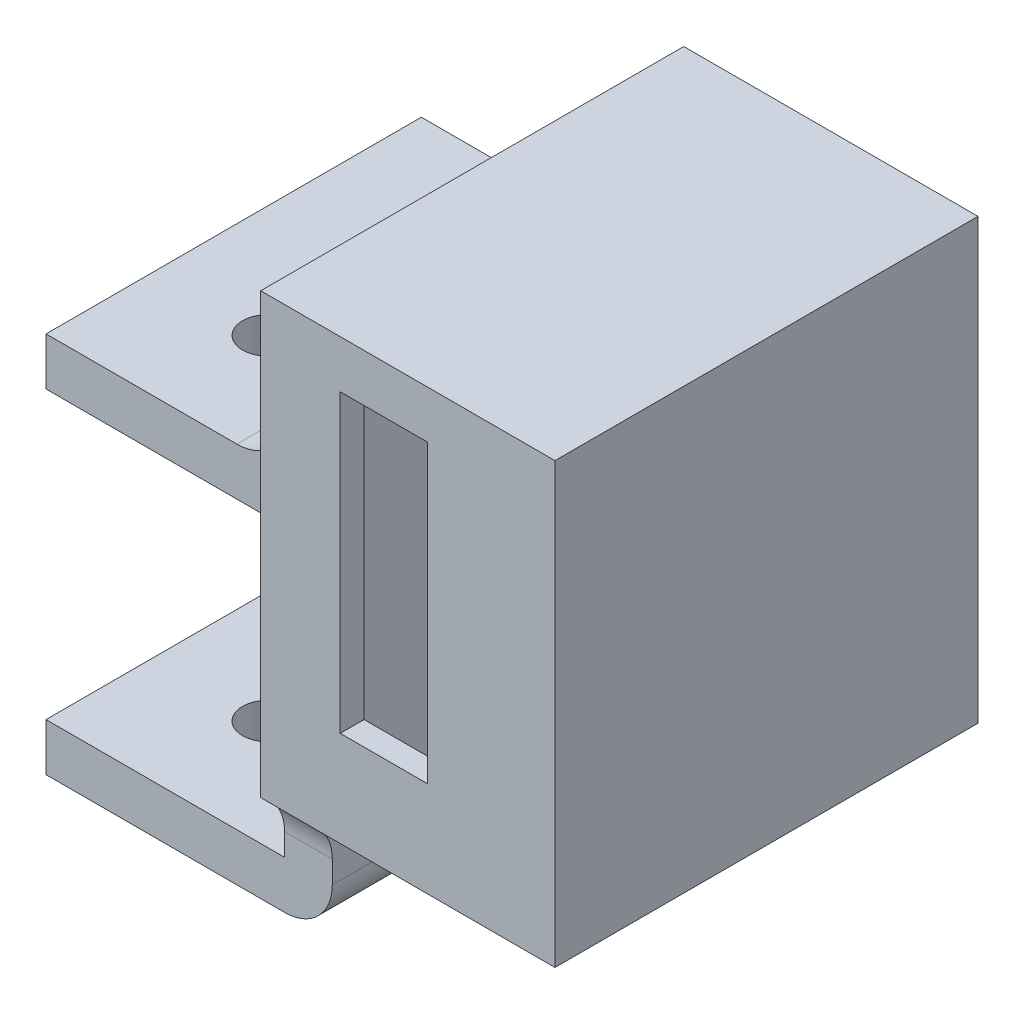
SolidWorks part; units mm, degrees
material "Custom Plastic"
ref_plane "Front Plane" through (0, 0, 0) normal (0, 0, 1) x (1, 0, 0)
ref_plane "Top Plane" through (0, 0, 0) normal (0, 1, 0) x (1, 0, 0)
ref_plane "Right Plane" through (0, 0, 0) normal (1, 0, 0) x (0, 0, -1)
sketch "Sketch1" plane through (0, 0, 0) normal (1, 0, 0) x (0, 0, -1)
  line L1 (-11.8, -12.3) -> (11.8, -12.3)
  line L2 (-11.8, -12.3) -> (-11.8, 12.3)
  line L3 (-11.8, 12.3) -> (11.8, 12.3)
  line L4 (11.8, -12.3) -> (11.8, 12.3)
  line L5 (-11.8, -12.3) -> (11.8, 12.3) construction
  line L6 (-11.8, 12.3) -> (11.8, -12.3) construction
  line L7 (-13.3, -13.8) -> (13.3, -13.8)
  line L8 (-13.3, -13.8) -> (-13.3, 13.8)
  line L9 (-13.3, 13.8) -> (13.3, 13.8)
  line L10 (13.3, -13.8) -> (13.3, 13.8)
  line L11 (-13.3, -13.8) -> (13.3, 13.8) construction
  line L12 (-13.3, 13.8) -> (13.3, -13.8) construction
  point P0 (0, 0)
  point P6 (0, 0)
  dimension "D1" = 24.6
  dimension "D2" = 23.6
  dimension "D3" = 26.6
  dimension "D4" = 24.6
  dimension "D5" = 27.6
extrude "Boss-Extrude1" add sketch "Sketch1" along normal blind 12.5
sketch "Sketch2" plane through (0, 0, 0) normal (-1, 0, 0) x (0, 0, 1)
  line L1 (-13.3, 13.8) -> (13.3, 13.8)
  line L2 (-13.3, 13.8) -> (-13.3, -13.8)
  line L3 (-13.3, -13.8) -> (13.3, -13.8)
  line L4 (13.3, 13.8) -> (13.3, -13.8)
extrude "Boss-Extrude2" add sketch "Sketch2" along normal blind 3
sketch "Sketch3" plane through (0, 0, -13.3) normal (0, 0, -1) x (-1, 0, 0)
sketch "Sketch4" plane through (12.5, 0, 0) normal (1, 0, 0) x (0, 0, -1)
  line L1 (-13.3, 13.8) -> (13.3, 13.8)
  line L2 (-13.3, 13.8) -> (-13.3, -13.8)
  line L3 (-13.3, -13.8) -> (13.3, -13.8)
  line L4 (13.3, 13.8) -> (13.3, -13.8)
extrude "Boss-Extrude3" add sketch "Sketch4" along normal blind 3
sketch "Sketch6" plane through (0, -13.8, 0) normal (0, -1, 0) x (-1, 0, 0)
  line L0 (0, 14.63) -> (0, -14.63) construction
  line L1 (0, -10.3) -> (-12.5, -10.3)
  line L2 (0, -10.3) -> (0, 10.3)
  line L3 (0, 10.3) -> (-12.5, 10.3)
  line L4 (-12.5, -10.3) -> (-12.5, 10.3)
  line L5 (-15.5, -13.3) -> (3, -13.3) construction
  line L6 (3, 13.3) -> (3, -13.3) construction
  line L7 (-15.5, -13.3) -> (-15.5, 13.3) construction
  line L8 (-15.5, 13.3) -> (3, 13.3) construction
  dimension "D1" = 3
  dimension "D2" = 3
  dimension "D3" = 3
  dimension "D4" = 3
extrude "Cut-Extrude1" cut sketch "Sketch6" against normal blind 3
sketch "Sketch7" plane through (0, -13.8, 0) normal (0, -1, 0) x (-1, 0, 0)
  line L0 (1.2891, -13.3) -> (1.2891, -4.9) construction
  line L1 (-15.5, -13.3) -> (3, -13.3) construction
  line L2 (1.2891, -4.9) -> (1.2891, 4.9) construction
  line L3 (1.2891, 4.9) -> (1.2891, 13.3) construction
  line L4 (-15.5, 13.3) -> (3, 13.3) construction
  line L5 (0, 14.63) -> (0, -14.63) construction
  line L6 (0, -7.4191) -> (12.54, -7.4191)
  line L7 (0, -7.4191) -> (0, 6.9729)
  line L8 (0, 6.9729) -> (12.54, 6.9729)
  line L9 (12.54, -7.4191) -> (12.54, 6.9729)
  dimension "D1" = 8.4
  dimension "D2" = 9.8
  dimension "D3" = 8.4
  dimension "D4" = 12.54
extrude "Boss-Extrude4" add sketch "Sketch7" along normal blind 7 and the other way blind 17
sketch "Sketch8" plane through (0, -20.8, 0) normal (0, -1, 0) x (-1, 0, 0)
  line L0 (12.54, 4.9005) -> (12.54, -4.9633)
  circle A0 centre (9.94, -4.9005) radius 1.6
  circle A1 centre (9.94, 4.8367) radius 1.6
  point P3 (12.54, -0.0633)
  point P8 (12.54, 0)
  dimension "D3" = 3.2
  dimension "D4" = 3.2
extrude "Cut-Extrude2" cut sketch "Sketch8" against normal through all contours A0 | A1 region at (-9.94, -20.8, 4.9005) region at (-9.94, -20.8, -4.8367)
sketch "Sketch10" plane through (0, 0, 7.4191) normal (0, 0, 1) x (1, 0, 0)
  line L0 (-12.54, 3.2) -> (-12.54, -20.8) construction
  line L1 (-12.54, 0.2) -> (-3, 0.2)
  line L2 (-12.54, 0.2) -> (-12.54, -17.8)
  line L3 (-12.54, -17.8) -> (-3, -17.8)
  line L4 (-3, 0.2) -> (-3, -17.8)
  line L5 (0, -20.8) -> (-12.54, -20.8) construction
  dimension "D1" = 3
  dimension "D2" = 3
  dimension "D3" = 18
extrude "Cut-Extrude3" cut sketch "Sketch10" against normal through all
sketch "Sketch11" plane through (0, 0, 13.3) normal (0, 0, 1) x (1, 0, 0)
  line L0 (-3, -13.8) -> (-3, 13.8) construction
  line L1 (2, 10.8) -> (7.5, 10.8)
  line L2 (2, 10.8) -> (2, -7.8)
  line L3 (2, -7.8) -> (7.5, -7.8)
  line L4 (7.5, 10.8) -> (7.5, -7.8)
  line L5 (15.5, 13.8) -> (15.5, -13.8) construction
  line L6 (15.5, 13.8) -> (-3, 13.8) construction
  line L7 (15.5, -13.8) -> (-3, -13.8) construction
  dimension "D1" = 5
  dimension "D2" = 8
  dimension "D3" = 3
  dimension "D4" = 6
sketch "Sketch14" plane through (0, -13.8, 0) normal (0, -1, 0) x (-1, 0, 0)
  line L0 (0, 14.63) -> (0, -14.63) construction
  line L1 (-12.5, -11.8) -> (0, -11.8)
  line L2 (-12.5, -11.8) -> (-12.5, 11.8)
  line L3 (-12.5, 11.8) -> (0, 11.8)
  line L4 (0, -11.8) -> (0, 11.8)
  line L5 (-15.5, -13.3) -> (3, -13.3) construction
  line L6 (-15.5, 13.3) -> (3, 13.3) construction
  dimension "D1" = 1.5
  dimension "D2" = 1.5
extrude "Cut-Extrude5" cut sketch "Sketch14" against normal blind 3
sketch "Sketch16" plane through (0, 0, 13.3) normal (0, 0, 1) x (1, 0, 0)
  line L1 (2, 10.8) -> (7.5, 10.8)
  line L2 (2, 10.8) -> (2, -7.8)
  line L3 (2, -7.8) -> (7.5, -7.8)
  line L4 (7.5, 10.8) -> (7.5, -7.8)
extrude "Cut-Extrude6" cut sketch "Sketch16" against normal blind 3
sketch "Sketch17" plane through (0, -13.8, 0) normal (0, -1, 0) x (-1, 0, 0)
  line L0 (0, 14.63) -> (0, -14.63) construction
  line L1 (-15.5, -13.3) -> (0, -13.3)
  line L2 (-15.5, -13.3) -> (-15.5, 13.3)
  line L3 (-15.5, 13.3) -> (0, 13.3)
  line L4 (0, -13.3) -> (0, 13.3)
  line L5 (-15.5, 13.3) -> (3, 13.3) construction
sketch "Sketch24" plane through (0, -13.8, 0) normal (0, -1, 0) x (-1, 0, 0)
  line L0 (0, -13.3) -> (0, 13.3) construction
  line L1 (3, -13.3) -> (0, -13.3)
  line L2 (3, -13.3) -> (3, -7.4191)
  line L3 (3, -7.4191) -> (0, -7.4191)
  line L4 (0, -13.3) -> (0, -7.4191)
  line L5 (0, -7.4191) -> (12.54, -7.4191) construction
extrude "Boss-Extrude7" add sketch "Sketch24" along normal blind 7
sketch "Sketch25" plane through (0, -13.8, 0) normal (0, -1, 0) x (-1, 0, 0)
  line L1 (0, 13.3) -> (3, 13.3)
  line L2 (0, 13.3) -> (0, 6.9729)
  line L3 (0, 6.9729) -> (3, 6.9729)
  line L4 (3, 13.3) -> (3, 6.9729)
extrude "Boss-Extrude8" add sketch "Sketch25" along normal blind 7
sketch "Sketch27" plane through (-3, 0, 0) normal (-1, 0, 0) x (0, 0, 1)
  line L0 (-13.3, 13.8) -> (-13.3, -20.8) construction
  line L1 (-13.3, -17.8) -> (13.3, -17.8)
  line L2 (-13.3, -17.8) -> (-13.3, -20.8)
  line L3 (-13.3, -20.8) -> (13.3, -20.8)
  line L4 (13.3, -17.8) -> (13.3, -20.8)
extrude "Boss-Extrude9" add sketch "Sketch27" along normal blind 20
sketch "Sketch29" plane through (0, -17.8, 0) normal (0, 1, 0) x (1, 0, 0)
  line L0 (-9.94, 4.8367) -> (-9.94, -4.9005)
  line L1 (-9.94, 4.8367) -> (-10.64, 4.8367) construction
  dimension "D1" = 0.7
sketch "Sketch30" plane through (0, -17.8, 0) normal (0, 1, 0) x (1, 0, 0)
  line L0 (-10.64, 4.8367) -> (-10.64, -4.9005)
sketch "Sketch32" plane through (-3, 0, 0) normal (-1, 0, 0) x (0, 0, 1)
  line L0 (-13.3, 13.8) -> (-13.3, -17.8) construction
  line L1 (-13.3, 3.2) -> (13.3, 3.2)
  line L2 (-13.3, 3.2) -> (-13.3, 0.2)
  line L3 (-13.3, 0.2) -> (13.3, 0.2)
  line L4 (13.3, 3.2) -> (13.3, 0.2)
  line L5 (13.3, 10.8) -> (13.3, -7.8) construction
extrude "Boss-Extrude10" add sketch "Sketch32" along normal blind 20
fillet "Fillet1" radius 3 1 edges at (0, -20.8, 0)
sketch "Sketch35" plane through (0, 0, 13.3) normal (0, 0, 1) x (1, 0, 0)
  line L1 (-3, 3.2) -> (-23, 3.2)
  line L2 (-3, 3.2) -> (-3, -20.8)
  line L3 (-3, -20.8) -> (-23, -20.8)
  line L4 (-23, 3.2) -> (-23, -20.8)
extrude "Cut-Extrude9" cut sketch "Sketch35" against normal blind 1.5
sketch "Sketch36" plane through (0, 0, 13.3) normal (0, 0, 1) x (1, 0, 0)
  line L0 (-3, -20.8) -> (-3, 13.8) construction
  line L1 (-3, -13.8) -> (0, -13.8)
  line L2 (-3, -13.8) -> (-3, -20.8)
  line L3 (-3, -20.8) -> (0, -20.8)
  line L4 (0, -13.8) -> (0, -20.8)
  line L5 (0, -14.63) -> (0, 14.63) construction
extrude "Cut-Extrude10" cut sketch "Sketch36" against normal blind 1.5
sketch "Sketch37" plane through (0, 0, -13.3) normal (0, 0, -1) x (-1, 0, 0)
  line L1 (23, 3.2) -> (3, 3.2)
  line L2 (23, 3.2) -> (23, -20.8)
  line L3 (23, -20.8) -> (3, -20.8)
  line L4 (3, 3.2) -> (3, -20.8)
extrude "Cut-Extrude11" cut sketch "Sketch37" against normal blind 1.5
sketch "Sketch38" plane through (0, 0, -13.3) normal (0, 0, -1) x (-1, 0, 0)
  line L0 (-15.5, -13.8) -> (0, -13.8) construction
  line L1 (3, -20.8) -> (0, -20.8)
  line L2 (3, -20.8) -> (3, -13.8)
  line L3 (3, -13.8) -> (0, -13.8)
  line L4 (0, -20.8) -> (0, -13.8)
  line L5 (0, 14.63) -> (0, -14.63) construction
extrude "Cut-Extrude12" cut sketch "Sketch38" against normal blind 1.5
fillet "Fillet3" radius 3 1 edges at (-1.5, -13.8, 11.8)
fillet "Fillet4" radius 3 1 edges at (-1.5, -13.8, -11.8)
fillet "Fillet5" radius 3 1 edges at (-3, 3.2, 0)
sketch "Sketch39" plane through (0, -20.8, 0) normal (0, -1, 0) x (-1, 0, 0)
  line L0 (3, 11.8) -> (23, 11.8) construction
  line L1 (23, -11.8) -> (18, -11.8)
  line L2 (23, -11.8) -> (23, 11.8)
  line L3 (23, 11.8) -> (18, 11.8)
  line L4 (18, -11.8) -> (18, 11.8)
  dimension "D1" = 5
extrude "Cut-Extrude13" cut sketch "Sketch39" against normal blind 24
sketch "Sketch40" plane through (0, -17.8, 0) normal (0, 1, 0) x (1, 0, 0)
  line L0 (-10.64, 4.8367) -> (-10.94, 4.8367)
  line L1 (-10.94, 4.8367) -> (-10.94, -4.9005)
  dimension "D1" = 0.3
sketch "Sketch41" plane through (0, -20.8, 0) normal (0, -1, 0) x (-1, 0, 0)
  circle A0 centre (10.94, -4.9005) radius 1.6
  circle A1 centre (10.94, 4.8367) radius 1.6
  dimension "D1" = 3.2
  dimension "D2" = 3.2
extrude "Cut-Extrude14" cut sketch "Sketch41" against normal blind 24
